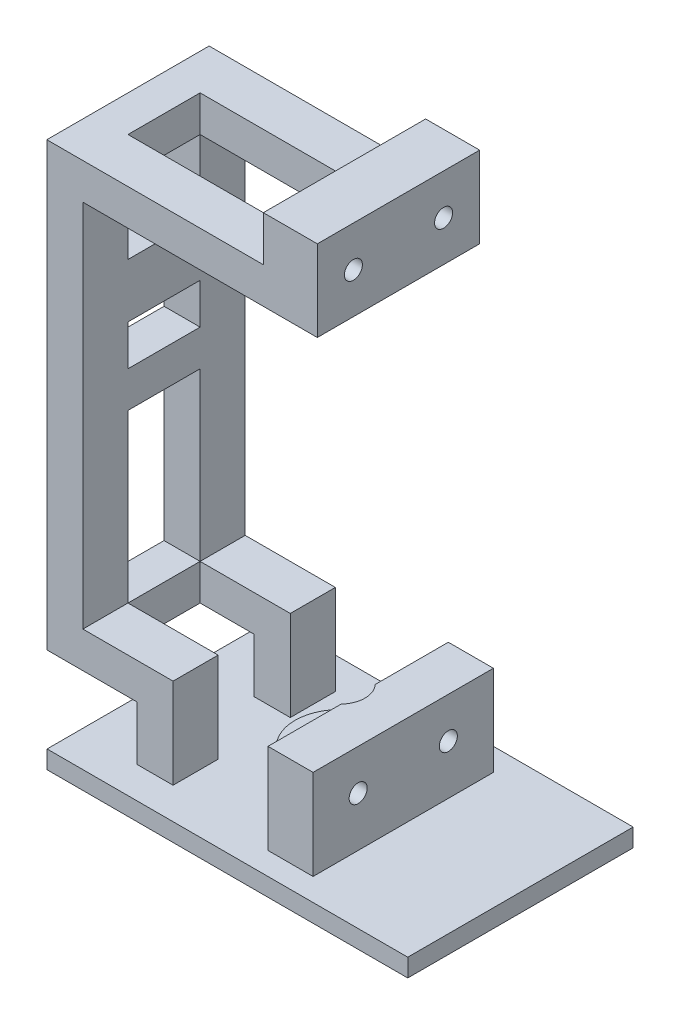
SolidWorks part; units mm, degrees
ref_plane "Front Plane" through (0, 0, 0) normal (0, 0, 1) x (1, 0, 0)
ref_plane "Top Plane" through (0, 0, 0) normal (0, 1, 0) x (1, 0, 0)
ref_plane "Right Plane" through (0, 0, 0) normal (1, 0, 0) x (0, 0, -1)
sketch "Sketch1" plane through (0, 0, 0) normal (0, 1, 0) x (1, 0, 0)
  line L0 (-20, 0) -> (20, 0) construction
  line L1 (-20, -12.5) -> (20, -12.5)
  line L2 (-20, -12.5) -> (-20, 12.5)
  line L3 (-20, 12.5) -> (20, 12.5)
  line L4 (20, -12.5) -> (20, 12.5)
  line L5 (-20, -12.5) -> (20, 12.5) construction
  line L6 (-20, 12.5) -> (20, -12.5) construction
  line L7 (0, 12.5) -> (0, -12.5) construction
  line L8 (-7.9106, 3.9553) -> (7.0894, 3.9553)
  line L9 (-7.9106, 3.9553) -> (-7.9106, -3.5447)
  line L10 (-7.9106, -3.5447) -> (7.0894, -3.5447)
  line L11 (7.0894, 3.9553) -> (7.0894, -3.5447)
  line L12 (-7.9106, 3.9553) -> (7.0894, -3.5447) construction
  line L13 (-7.9106, -3.5447) -> (7.0894, 3.9553) construction
  circle A0 centre (0, 7.9553) radius 1
  circle A1 centre (0, -7.5447) radius 1
  circle A2 centre (16, 0) radius 1
  circle A3 centre (-16, 0) radius 1
  point P0 (0, 0)
  point P8 (0, 0)
  dimension "D5" = 2
  dimension "D7" = 2
  dimension "D9" = 2
  dimension "D1" = 40
  dimension "D2" = 25
  dimension "D3" = 15
  dimension "D4" = 7.5
  dimension "D6" = 4
  dimension "D8" = 4
  dimension "D10" = 16
extrude "Boss-Extrude1" add sketch "Sketch1" along normal blind 2 contours L2 L1 L4 L3
sketch "Sketch2" plane through (0, 2, 0) normal (0, 1, 0) x (1, 0, 0)
  line L1 (2, 10) -> (7, 10)
  line L2 (2, 10) -> (2, -10)
  line L3 (2, -10) -> (7, -10)
  line L4 (7, 10) -> (7, -10)
  line L5 (20, -12.5) -> (20, 12.5) construction
  point P6 (20, 0)
  point P7 (7, 0)
  dimension "D1" = 20
  dimension "D2" = 13
  dimension "D3" = 5
extrude "Boss-Extrude2" add sketch "Sketch2" along normal blind 10
sketch "Sketch4" plane through (7, 0, 0) normal (1, 0, 0) x (0, 0, -1)
  line L0 (-7.046, 10.16) -> (2.954, 10.16) construction
  line L3 (-10, 12) -> (9.965, 12)
  line L4 (-10, 12) -> (-10, 6)
  line L5 (-10, 6) -> (9.965, 6)
  line L6 (9.965, 12) -> (9.965, 6)
  dimension "D1" = 10
  dimension "D2" = 6
extrude "Boss-Extrude3" add sketch "Sketch4" against normal up to surface (5 mm away) up to face at (2, 7, 0)
sketch "Sketch5" plane through (7, 0, 0) normal (1, 0, 0) x (0, 0, -1)
  line L0 (-5, 7.5) -> (5, 7.5) construction
  line L1 (-10, 12) -> (10, 12) construction
  circle A0 centre (5, 7.5) radius 1
  circle A1 centre (-5, 7.5) radius 1
  point P4 (0, 12)
  point P5 (0, 7.5)
  dimension "D2" = 2
  dimension "D3" = 2
  dimension "D1" = 10
  dimension "D4" = 4.5
extrude "Cut-Extrude2" cut sketch "Sketch5" against normal up to surface (5 mm away) up to face at (2, 7, 0)
sketch "Sketch6" plane through (0, 2, 0) normal (0, 1, 0) x (1, 0, 0)
  line L0 (-20, 12.5) -> (-20, -12.5) construction
  line L1 (-13.5277, 9) -> (-9.5277, 9)
  line L2 (-13.5277, 9) -> (-13.5277, -9)
  line L3 (-13.5277, -9) -> (-9.5277, -9)
  line L4 (-9.5277, 9) -> (-9.5277, -9)
  line L10 (-13.5277, 4) -> (-9.5277, 4)
  line L11 (-13.5277, 4) -> (-13.5277, -4)
  line L12 (-13.5277, -4) -> (-9.5277, -4)
  line L13 (-9.5277, 4) -> (-9.5277, -4)
  point P6 (-20, 0)
  point P7 (-13.5277, 0)
  point P12 (-13.5277, 0)
  dimension "D1" = 4
  dimension "D2" = 18
  dimension "D3" = 4
  dimension "D4" = 8
extrude "Boss-Extrude4" add sketch "Sketch6" along normal blind 10 contours L12 L2 L3 L4 | L2 L10 L4 L1 region at (-11.5277, 2, -6.5) region at (-11.5277, 2, 6.5)
sketch "Sketch8" plane through (-13.5277, 0, 0) normal (-1, 0, 0) x (0, 0, 1)
  line L1 (-9, 12) -> (-4, 12)
  line L2 (-9, 12) -> (-9, 8)
  line L3 (-9, 8) -> (-4, 8)
  line L4 (-4, 12) -> (-4, 8)
  dimension "D1" = 5
  dimension "D2" = 4
ref_plane "Plane1" through (0, 0, 0) normal (0, 0, -1) x (-1, 0, 0)
extrude "Boss-Extrude5" add sketch "Sketch8" along normal blind 10
mirror "Mirror1" about plane through (0, 0, 0) normal (0, 0, -1) of "Boss-Extrude5"
sketch "Sketch9" plane through (0, 12, 0) normal (0, 1, 0) x (1, 0, 0)
  line L0 (-23.5277, 4) -> (-9.5277, 4) construction
  line L1 (-23.5277, 9) -> (-19.5277, 9)
  line L2 (-23.5277, 9) -> (-23.5277, 4)
  line L3 (-23.5277, 4) -> (-19.5277, 4)
  line L4 (-19.5277, 9) -> (-19.5277, 4)
  dimension "D1" = 4
  dimension "D2" = 0
extrude "Boss-Extrude6" add sketch "Sketch9" along normal blind 45
mirror "Mirror2" about plane through (0, 0, 0) normal (0, 0, -1) of "Boss-Extrude5"
mirror "Mirror3" about plane through (0, 0, 0) normal (0, 0, -1) of "Boss-Extrude6"
sketch "Sketch12" plane through (-23.5277, 0, 0) normal (-1, 0, 0) x (0, 0, 1)
  line L0 (9, 57) -> (9, 8) construction
  line L1 (-9, 57) -> (9, 57)
  line L2 (-9, 57) -> (-9, 53)
  line L3 (-9, 53) -> (9, 53)
  line L4 (9, 57) -> (9, 53)
  line L5 (-10, 12) -> (10, 12) construction
  line L6 (-9, 8) -> (9, 8)
  line L7 (-9, 8) -> (-9, 12)
  line L8 (-9, 12) -> (9, 12)
  line L9 (9, 8) -> (9, 12)
  line L10 (-9, 32.5) -> (9, 32.5) construction
  line L11 (-9, 57) -> (-9, 8) construction
  line L13 (-9, 30.5) -> (9, 30.5)
  line L14 (-9, 30.5) -> (-9, 34.5)
  line L15 (-9, 34.5) -> (9, 34.5)
  line L16 (9, 30.5) -> (9, 34.5)
  line L17 (-9, 30.5) -> (9, 34.5) construction
  line L18 (-9, 34.5) -> (9, 30.5) construction
  point P18 (0, 32.5)
  dimension "D1" = 4
  dimension "D2" = 4
  dimension "D3" = 4
extrude "Boss-Extrude8" add sketch "Sketch12" against normal up to surface (4 mm away) up to face at (-19.5277, 34.5, 6.5)
sketch "Sketch13" plane through (-19.5277, 0, 0) normal (1, 0, 0) x (0, 0, -1)
  line L1 (-9, 57) -> (-4, 57)
  line L2 (-9, 57) -> (-9, 53)
  line L3 (-9, 53) -> (-4, 53)
  line L4 (-4, 57) -> (-4, 53)
  line L5 (9, 57) -> (4, 57)
  line L6 (9, 57) -> (9, 53)
  line L7 (9, 53) -> (4, 53)
  line L8 (4, 57) -> (4, 53)
extrude "Boss-Extrude9" add sketch "Sketch13" along normal blind 26
sketch "Sketch14" plane through (6.4723, 0, 0) normal (1, 0, 0) x (0, 0, -1)
  line L0 (-9, 57) -> (9, 57)
  line L1 (-9, 57) -> (-9, 53)
  line L2 (9, 57) -> (9, 53)
  line L3 (-9, 53) -> (9, 53)
  line L4 (-9, 53) -> (-4, 53) construction
extrude "Boss-Extrude10" add sketch "Sketch14" against normal blind 6
sketch "Sketch15" plane through (6.4723, 0, 0) normal (1, 0, 0) x (0, 0, -1)
  line L0 (-5, 57.5) -> (5, 57.5) construction
  line L1 (-9, 53) -> (9, 53) construction
  line L2 (-5, 7.5) -> (-5, 57.5) construction
  circle A0 centre (-5, 57.5) radius 1
  circle A1 centre (5, 57.5) radius 1
  dimension "D3" = 2
  dimension "D4" = 2
  dimension "D1" = 10
  dimension "D2" = 4.5
sketch "Sketch16" plane through (0, 57, 0) normal (0, 1, 0) x (1, 0, 0)
  line L0 (6.4723, 9) -> (6.4723, -9)
  line L1 (6.4723, 9) -> (0.4841, 9)
  line L2 (6.4723, -9) -> (0.4841, -9)
  line L3 (0.4841, 9) -> (0.4841, -9)
extrude "Boss-Extrude11" add sketch "Sketch16" along normal blind 5
extrude "Cut-Extrude3" cut sketch "Sketch15" against normal blind 6
sketch "Sketch17" plane through (0, 0, 0) normal (0, -1, 0) x (1, 0, 0)
  circle A0 centre (0, 0) radius 3
  circle A1 centre (0, 0) radius 5
  dimension "D1" = 6
  dimension "D2" = 2
sketch "Sketch18" plane through (-23.5277, 0, 0) normal (-1, 0, 0) x (0, 0, 1)
  line L0 (0, 0) -> (0, 62) construction
  line L1 (-9, 62) -> (9, 62) construction
  line L2 (-17.0412, 42) -> (24.329, 42) construction
  line L3 (12.5, 0) -> (-12.5, 0) construction
  dimension "42" = 42
extrude "Cut-Extrude5" cut sketch "Sketch17" against normal blind 6 contours A0
ref_plane "Plane2" through (0, 1, 0) normal (0, -1, 0) x (-1, 0, 0)
ref_plane "Plane3" through (0, 3, 0) normal (0, 1, 0) x (1, 0, 0)
sketch "Sketch20" plane through (0, 3, 0) normal (0, 1, 0) x (1, 0, 0)
  circle A0 centre (0, 0) radius 3
  circle A1 centre (0, 0) radius 5
  dimension "D1" = 6
  dimension "D2" = 2
sketch "Sketch23" plane through (20, 0, 0) normal (1, 0, 0) x (0, 0, -1)
  line L0 (-12.5, 2) -> (-10.5, 2)
  line L1 (-12.5, 2) -> (-12.5, 59.5)
  line L2 (12.5, 2) -> (12.5, 59.5)
  line L3 (-10.5, 2) -> (-10.5, 59.5)
  line L4 (-12.5, 2) -> (12.5, 2) construction
  line L5 (10.5, 2) -> (10.5, 59.5)
  line L6 (10.5, 2) -> (12.5, 2)
  arc A0 (12.5, 59.5) -> (-12.5, 59.5) centre (0, 59.5) ccw
  arc A1 (10.5, 59.5) -> (-10.5, 59.5) centre (0, 59.5) ccw
  dimension "D2" = 2
sketch "Sketch24" plane through (-23.5277, 0, 0) normal (-1, 0, 0) x (0, 0, 1)
  line L0 (0, 0) -> (0, 62) construction
  line L1 (-17.0412, 42) -> (24.329, 42) construction
  line L2 (4, 34.5) -> (4, 53) construction
  line L3 (-4, 39) -> (4, 39)
  line L4 (-4, 39) -> (-4, 45)
  line L5 (-4, 45) -> (4, 45)
  line L6 (4, 39) -> (4, 45)
  line L7 (-4, 39) -> (4, 45) construction
  line L8 (-4, 45) -> (4, 39) construction
  circle A0 centre (0, 42) radius 3
  line M1 (4, 53) -> (4, 34.5)
  line M3 (-4, 34.5) -> (-4, 53)
  dimension "D1" = 6
extrude "Boss-Extrude18" add sketch "Sketch24" against normal blind 4 contours A0 | A0 L5 L3 M3 | A0 L3 L5 M1 region at (-23.5277, 42, -3.0417) region at (-23.5277, 42, 3.0417) region at (-23.5277, 42, 0)
extrude "Boss-Extrude19" add sketch "Sketch24<4>" along normal blind 6 contours A0 region at (-23.5277, 42, 0)
sketch "Sketch24<4>" plane through (-23.5277, 0, 0) normal (-1, 0, 0) x (0, 0, 1) same geometry as "Sketch24"
extrude "Boss-Extrude20" add sketch "Sketch20" against normal blind 1
sketch "Sketch26" plane through (0, 3, 0) normal (0, 1, 0) x (1, 0, 0)
  circle A0 centre (0, 0) radius 2.9983
  circle A1 centre (0, 0) radius 5
  circle A2 centre (0, 0) radius 1.5
  line M1 (2, -4.5826) -> (2, -2.2361)
  arc M2 (2, -2.2361) -> (2, 2.2361) centre (0, 0) cw
  line M3 (2, 2.2361) -> (2, 4.5826)
  arc M4 (2, 4.5826) -> (2, -4.5826) centre (0, 0) ccw
  dimension "D1" = 3
extrude "Boss-Extrude21" add sketch "Sketch26" along normal blind 1 contours A0 A2 | M4 M1 M2 M3 region at (-2.9135, 3, 0) region at (1.8779, 3, -3.4093)
sketch "Sketch27" plane through (0, 4, 0) normal (0, 1, 0) x (1, 0, 0)
  circle A0 centre (0, 0) radius 5
  circle A1 centre (0, 0) radius 2.75
  dimension "D1" = 5.5
extrude "Boss-Extrude22" add sketch "Sketch27" along normal blind 2
sketch "Sketch28" plane through (0, 6, 0) normal (0, 1, 0) x (1, 0, 0)
  circle A0 centre (0, 0) radius 2.75
extrude "Cut-Extrude10" cut sketch "Sketch28" along normal blind 10
